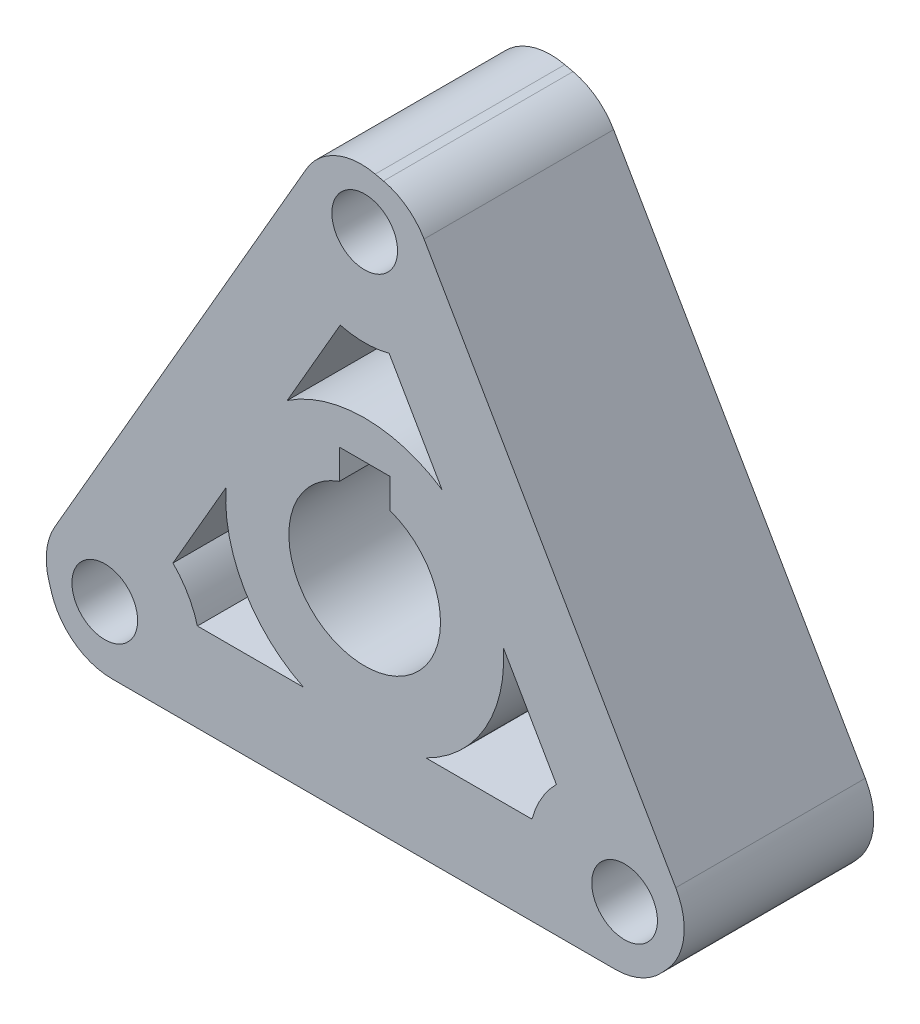
SolidWorks part; units mm, degrees
ref_plane "正面" through (0, 0, 0) normal (0, 0, 1) x (1, 0, 0)
ref_plane "平面" through (0, 0, 0) normal (0, 1, 0) x (1, 0, 0)
ref_plane "右側面" through (0, 0, 0) normal (1, 0, 0) x (0, 0, -1)
sketch "ｽｹｯﾁ1" plane through (0, 0, 0) normal (0, 0, 1) x (1, 0, 0)
  line L0 (0, 0) -> (-20.5681, -11.875) construction
  line L1 (0, 23.75) -> (-20.5681, -11.875) construction
  line L2 (-20.5681, -11.875) -> (20.5681, -11.875) construction
  line L3 (20.5681, -11.875) -> (0, 23.75) construction
  line L4 (-4.6132, 25.7596) -> (-24.5285, -8.7346)
  line L5 (-20.0019, -16.875) -> (19.8287, -16.875)
  line L6 (24.6151, -8.8846) -> (4.6999, 25.6096)
  line L7 (0, 33.75) -> (-29.2284, -16.875) construction
  line L8 (29.2284, -16.875) -> (0, 33.75) construction
  line L9 (1.4894, 27.9826) -> (0.8365, 28.1326)
  line L10 (-29.2284, -16.875) -> (29.2284, -16.875) construction
  line L11 (-24.9784, -12.7015) -> (-24.7818, -13.3419)
  line L12 (23.489, -15.2812) -> (23.9453, -14.7908)
  line L14 (-2, 4) -> (2, 4)
  line L15 (-2, 4) -> (-2, 8)
  line L16 (-2, 8) -> (2, 8)
  line L17 (2, 4) -> (2, 8)
  line L18 (-2, 4) -> (2, 8) construction
  line L19 (-2, 8) -> (2, 4) construction
  circle A0 centre (0, 0) radius 11.875 construction
  circle A1 centre (0, 23.75) radius 2.6
  circle A2 centre (20.5681, -11.875) radius 2.6
  circle A3 centre (-20.5681, -11.875) radius 2.6
  circle A4 centre (0, 0) radius 6
  arc A5 (-24.9784, -12.7015) -> (-24.5285, -8.7346) centre (-20.1984, -11.2346) cw
  arc A6 (-24.7818, -13.3419) -> (-20.0019, -16.875) centre (-20.0019, -11.875) ccw
  arc A7 (23.489, -15.2812) -> (19.8287, -16.875) centre (19.8287, -11.875) cw
  arc A8 (23.9453, -14.7908) -> (24.6151, -8.8846) centre (20.285, -11.3846) ccw
  arc A9 (1.4894, 27.9826) -> (4.6999, 25.6096) centre (0.3697, 23.1096) cw
  arc A10 (0.8365, 28.1326) -> (-4.6132, 25.7596) centre (-0.2831, 23.2596) ccw
  point P31 (0, 6)
  dimension "D1" = 5.2
  dimension "D2" = 5.2
  dimension "D3" = 5.2
  dimension "D5" = 12
  dimension "D7" = 5
  dimension "D4" = 23.75
  dimension "D8" = 4
  dimension "D9" = 4
  dimension "D6" = 5
extrude "ﾎﾞｽ - 押し出し1" add sketch "ｽｹｯﾁ1" along normal blind 15 contours L9 A10 L4 A5 L11 A6 L5 A7 L12 A8 L6 A9 A1 A2 A3 A4 L15 L16 L17 region at (-2.0089, 27.223, 0)
sketch "ｽｹｯﾁ3" plane through (0, -16.875, 0) normal (0, -1, 0) x (1, 0, 0)
  line L0 (-20.0019, 0) -> (19.8287, 0) construction
  circle A0 centre (0, 5) radius 1.5
  dimension "D1" = 5
  dimension "D2" = 3
extrude "ｶｯﾄ - 押し出し1" cut sketch "ｽｹｯﾁ3" against normal up to next
sketch "ｽｹｯﾁ4" plane through (0, -16.875, 0) normal (0, -1, 0) x (1, 0, 0)
  circle A0 centre (0, 5) radius 3.1
  dimension "D1" = 6.2
extrude "ｶｯﾄ - 押し出し2" cut sketch "ｽｹｯﾁ4" against normal blind 3
sketch "ｽｹｯﾁ5" plane through (0, 0, 0) normal (0, 0, -1) x (-1, 0, 0)
  line L12 (0, 19.75) -> (-17.104, -9.875)
  line L13 (-17.104, -9.875) -> (17.104, -9.875)
  line L14 (17.104, -9.875) -> (0, 19.75)
  line L15 (0, 19.75) -> (-17.104, -9.875)
  line L16 (-17.104, -9.875) -> (17.104, -9.875)
  line L17 (17.104, -9.875) -> (0, 19.75)
  circle A12 centre (0, 23.75) radius 7.6
  circle A13 centre (0, 23.75) radius 7.6
  circle A15 centre (-20.5681, -11.875) radius 7.6
  circle A16 centre (-20.5681, -11.875) radius 7.6
  circle A18 centre (20.5681, -11.875) radius 7.6
  circle A19 centre (20.5681, -11.875) radius 7.6
  circle A20 centre (0, 0) radius 11
  dimension "D4" = 22
  dimension "D1" = 5
  dimension "D2" = 5
  dimension "D3" = 5
  dimension "D5" = 7
extrude "ｶｯﾄ - 押し出し3" cut sketch "ｽｹｯﾁ5" against normal through all contours A20 L15 A16 L16 | A20 L17 A13 L15 | A20 L16 A19 L17 region at (0, 12.8976, 0) region at (11.1697, -6.4488, 0) region at (-11.1697, -6.4488, 0)
